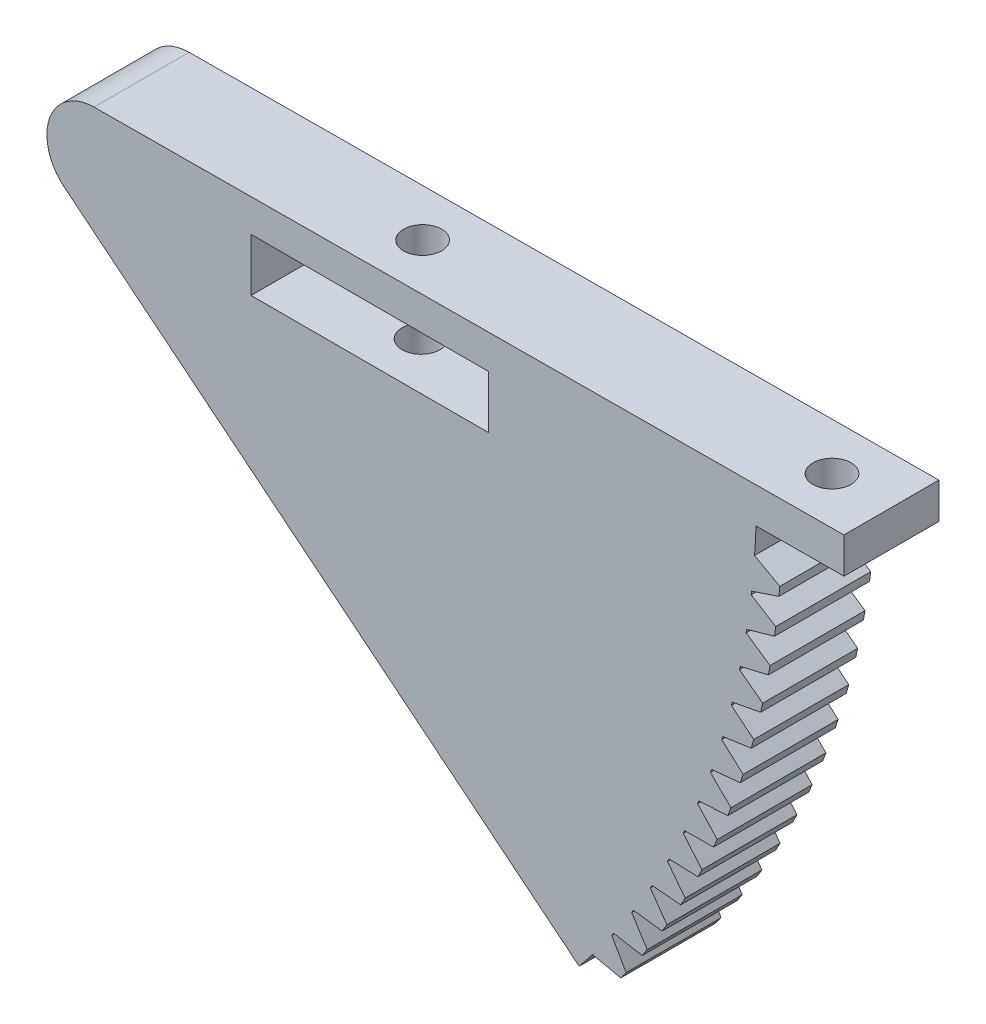
SolidWorks part; units mm, degrees
ref_plane "Front Plane" through (0, 0, 0) normal (0, 0, 1) x (1, 0, 0)
ref_plane "Top Plane" through (0, 0, 0) normal (0, 1, 0) x (1, 0, 0)
ref_plane "Right Plane" through (0, 0, 0) normal (1, 0, 0) x (0, 0, -1)
sketch "Sketch9" plane through (0, 0, 35.1194) normal (0, 0, 1) x (1, 0, 0)
  line L0 (9.5455, 41.7443) -> (-57.4302, 41.3512)
  line L1 (-57.4302, 41.3512) -> (-12.111, 4.6246)
  line L2 (9.5455, 41.7443) -> (16.8954, 41.7874)
  line L3 (-12.111, 4.6246) -> (-5.3951, -0.818)
  line L4 (16.8954, 41.7874) -> (16.913, 38.7875)
  line L5 (16.913, 38.7875) -> (9.4959, 38.7439)
  line L6 (11.4996, 35.3389) -> (9.3725, 36.5241)
  line L7 (11.4996, 35.3389) -> (11.4285, 34.5722)
  line L8 (11.4285, 34.5722) -> (9.1195, 33.7989)
  arc A0 (-5.3951, -0.818) -> (9.1195, 33.7989) centre (-57.4302, 41.3512) ccw
  arc A1 (9.3725, 36.5241) -> (9.4959, 38.7439) centre (-57.4302, 41.3512) ccw
  dimension "D3" = 246.18
  dimension "D1" = 0.77
  dimension "D2" = 246.18
extrude "Boss-Extrude1" add sketch "Sketch9" against normal blind 8
sketch "Sketch10" plane through (0, 0, 35.1194) normal (0, 0, 1) x (1, 0, 0)
  line L2 (-33.0323, 38.7462) -> (-13.0323, 38.7462)
  line L3 (-33.0323, 38.7462) -> (-33.0323, 34.2883)
  line L4 (-33.0323, 34.2883) -> (-13.0323, 34.2883)
  line L5 (-13.0323, 38.7462) -> (-13.0323, 34.2883)
  dimension "D1" = 20
extrude "Cut-Extrude1" cut sketch "Sketch10" against normal blind 8
sketch "Sketch11" plane through (0.7472, 41.9146, 0) normal (0.0178, 0.9998, 0) x (0.9998, -0.0178, 0)
  line L0 (6.4172, -31.1194) -> (-38.5283, -31.1194) construction
  line L1 (6.4172, -35.1194) -> (6.4172, -27.1194) construction
  circle A0 centre (-23.3207, -31.1194) radius 1.6
extrude "Cut-Extrude2" cut sketch "Sketch11" against normal blind 17
pattern_circular "CirPattern1" count 13 every 2.583 about axis through (-57.4302, 41.3512, 35.1194) along (0, 0, 1) reverse direction yes of face at (10.274, 34.1856, 31.1194) of face at (11.4641, 34.9556, 31.1194) of face at (10.4361, 35.9315, 31.1194)
fillet "Fillet1" radius 4 1 edges at (-57.4302, 41.3512, 31.1194)
sketch "Sketch13" plane through (-0.2446, 41.6868, 0) normal (-0.0059, 1, 0) x (1, 0.0059, 0)
  circle A0 centre (12.1403, -31.1194) radius 1.6
extrude "Cut-Extrude3" cut sketch "Sketch13" against normal blind 4
